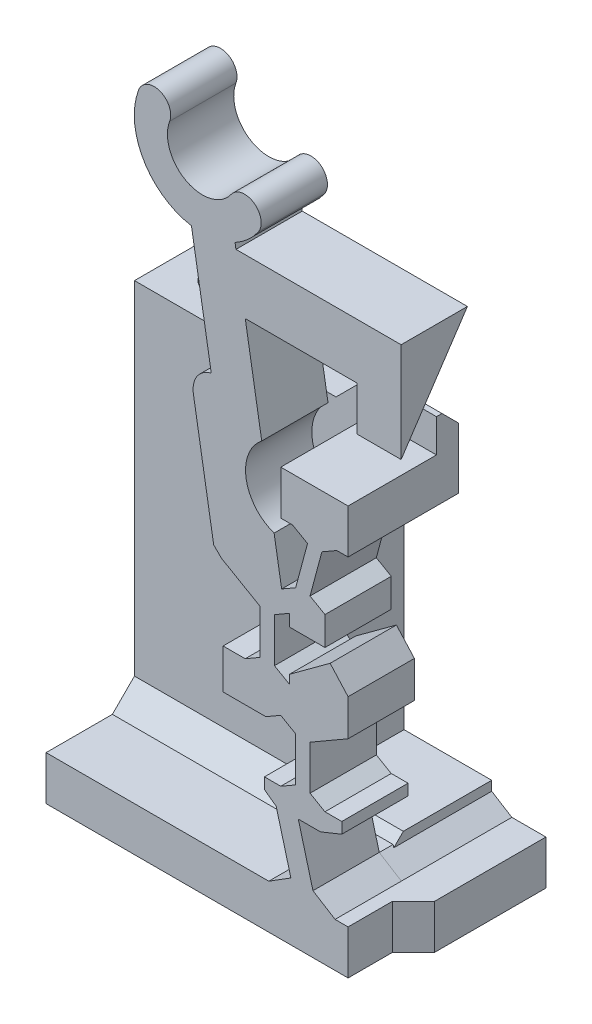
SolidWorks part; units mm, degrees
material "Nylon 6/12"
ref_plane "Front Plane" through (0, 0, 0) normal (0, 0, 1) x (1, 0, 0)
ref_plane "Top Plane" through (0, 0, 0) normal (0, 1, 0) x (1, 0, 0)
ref_plane "Right Plane" through (0, 0, 0) normal (1, 0, 0) x (0, 0, -1)
sketch "Sketch-SkeletonConfigUp" plane through (0, 0, 0) normal (0, 0, 1) x (1, 0, 0)
  line L0 (0, 0) -> (0, -50000) construction
  line L1 (0, 0) -> (4.5811, 6.2164) construction
  line L2 (9.8143, 13.3177) -> (4.5811, 13.945) construction
  line L3 (4.5811, 13.945) -> (2.9713, 10.4094) construction
  line L4 (2.9713, 10.4094) -> (4.5811, 6.2164) construction
  line L5 (4.5811, 13.945) -> (6.2429, 19.1409) construction
  line L6 (2.9713, 10.4094) -> (0.0405, 27.8193) construction
  line L7 (4.5811, 6.2164) -> (9.8143, 13.3177) construction
  line L8 (-587.3593, -797.0242) -> (9.8143, 13.3177) construction
  dimension "D2" = 7.7221
  dimension "D3" = 8.8212
  dimension "D4" = 5.2707
  dimension "D5" = 119.553
  dimension "D6" = 3.8848
  dimension "D7" = 5.4552
  dimension "D8" = 17.6549
  dimension "D9" = 4.4914
  dimension "D10" = 6.745
  dimension "D11" = 145.964
  dimension "D12" = 143.612
sketch "Sketch-SkeletonConfigDown" plane through (0, 0, 0) normal (0, 0, 1) x (1, 0, 0)
  line L0 (0, 0) -> (0, -50000) construction
  line L1 (0, 0) -> (4.5811, 6.2164) construction
  line L2 (9.8143, 13.3177) -> (4.5811, 13.945) construction
  line L3 (4.5811, 13.945) -> (6.1909, 10.4094) construction
  line L4 (6.1909, 10.4094) -> (4.5811, 6.2164) construction
  line L5 (4.5811, 13.945) -> (1.753, 18.6098) construction
  line L6 (6.1909, 10.4094) -> (-8.8652, 19.6294) construction
  line L7 (4.5811, 6.2164) -> (9.8143, 13.3177) construction
  line L8 (-589.9357, -800.5203) -> (9.8143, 13.3177) construction
  dimension "D2" = 7.7221
  dimension "D3" = 8.8212
  dimension "D4" = 5.2707
  dimension "D5" = 119.553
  dimension "D6" = 3.8848
  dimension "D7" = 5.4552
  dimension "D8" = 17.6549
  dimension "D9" = 4.4914
  dimension "D10" = 6.745
  dimension "D11" = 145.964
  dimension "D1" = 143.612
ref_plane "Plane-Cam Base" through (9.128, 0, 0) normal (1, 0, 0) x (0, 0, -1)
ref_plane "Plane-Down-to-Up Derailleur Clearance" through (6.628, 0, 0) normal (1, 0, 0) x (0, 0, -1)
ref_plane "Plane-Cam Cavity Roof" through (5.128, 0, 0) normal (1, 0, 0) x (0, 0, -1)
sketch "Sketch-SwitchBossUp" plane through (0, 0, 0) normal (0, 0, 1) x (1, 0, 0)
  line L0 (3.5811, 11.4759) -> (3.5811, 12.945) construction
  line L5 (5.5811, 12.5552) -> (5.5811, 11.263)
  line L7 (1.5115, 25.1048) -> (1.5536, 24.8548)
  line L8 (-0.4607, 24.7728) -> (0.4359, 19.4465)
  line L9 (2.9713, 10.4094) -> (0.0405, 27.8193) construction
  line L11 (0.1364, 21.2256) -> (2.1086, 21.5576) construction
  line L15 (6.628, -23.7286) -> (6.628, 23.7286) construction
  line L16 (2.9713, 10.4094) -> (4.5811, 6.2164) construction
  line L17 (3.5811, 12.945) -> (3.5811, 14.945) construction
  line L18 (5.5811, 12.945) -> (5.5811, 14.945) construction
  line L19 (4.2561, 13.945) -> (4.9061, 13.945) construction
  line L20 (3.5811, 14.945) -> (5.5811, 14.945) construction
  line L21 (3.5811, 12.945) -> (5.5811, 12.945) construction
  line L22 (4.5811, 12.945) -> (4.5811, 14.945) construction
  line L23 (4.5811, 6.2164) -> (8.5405, 7.1023) construction
  line L24 (1.9713, 9.4094) -> (1.9713, 11.4094) construction
  line L25 (3.9713, 9.4094) -> (3.9713, 11.4094) construction
  line L26 (3.9713, 9.4094) -> (1.9713, 9.4094) construction
  line L27 (1.9713, 11.4094) -> (3.9713, 11.4094) construction
  line L28 (3.5811, 7.2164) -> (5.5811, 7.2164) construction
  line L29 (3.5811, 7.2164) -> (3.5811, 5.2164) construction
  line L30 (5.5811, 7.2164) -> (5.5811, 5.2164) construction
  line L31 (3.5811, 5.2164) -> (5.5811, 5.2164) construction
  line L32 (4.9061, 6.2164) -> (4.2561, 6.2164) construction
  line L40 (3.2963, 10.4094) -> (2.6463, 10.4094) construction
  line L66 (0.0405, 27.8193) -> (0.0405, 50027.8193) construction
  line L74 (0.5455, 12.7717) -> (-0.3728, 18.2264)
  line L75 (0.3841, 13.7302) -> (2.3564, 14.0622) construction
  line L76 (5.5811, 11.263) -> (5.5811, 12.5552) construction
  line L77 (5.5811, 7.6061) -> (6.628, 8.2105)
  line L80 (5.8152, 10.763) -> (6.628, 9.8603)
  line L81 (9.128, 1033.2419) -> (9.128, 20.0586) construction
  line L85 (6.9307, 9.5241) -> (8.5405, 7.7363) construction
  line L88 (5.7256, 17.3347) -> (6.628, 17.3347)
  line L92 (3.7762, 8.3129) -> (6.9307, 9.5241) construction
  line L98 (1.9713, 9.0197) -> (0.9713, 9.0197)
  line L99 (0.9713, 9.0197) -> (0.9713, 7.2164)
  line L100 (0.9713, 7.2164) -> (2.9061, 7.2164)
  line L101 (4.5811, 6.2164) -> (6.9307, 9.5241) construction
  line L103 (0.0405, 27.8193) -> (1.9448, 26.4638) construction
  line L104 (6.9307, 9.5241) -> (8.5405, 7.7363) construction
  line L107 (1.9713, 9.4094) -> (1.9713, 9.0197) construction
  line L109 (0.0405, 27.8193) -> (-2.1498, 28.6358) construction
  line L111 (6.628, 9.8603) -> (6.628, 8.2105)
  line L112 (6.628, 9.8603) -> (6.9307, 9.5241) construction
  line L113 (2.8424, 4.8267) -> (2.8424, 4.3267)
  line L114 (7.3693, 7.7363) -> (7.3563, 7.7363) construction
  line L121 (5.0383, -1.1653) -> (5.0383, 1.4614) construction
  line L122 (9.028, 22.3548) -> (9.028, 20.3548)
  line L127 (5.5811, 15.3347) -> (5.5811, 14.945) construction
  line L130 (6.0388, 0.837) -> (6.628, 0.837)
  line L132 (2.8424, 4.3267) -> (3.3749, 3.937)
  line L133 (2.9713, 10.4094) -> (6.1909, 10.4094) construction
  line L134 (4.5811, 10.4094) -> (4.5811, 13.945) construction
  line L135 (4.5811, 10.4094) -> (4.5811, 6.2164) construction
  line L136 (0.8973, 12.4192) -> (0.5455, 12.7717)
  line L137 (3.9713, 9.4094) -> (5.5811, 7.2164) construction
  line L139 (5.8152, 10.763) -> (3.9713, 9.4094)
  line L141 (4.0386, 1.4604) -> (3.0388, 0.8347)
  line L142 (3.0388, 0.8347) -> (3.0388, -1.1653)
  line L143 (9.128, 20.0586) -> (9.128, 18.3333) construction
  line L145 (9.128, 16.6071) -> (9.128, -49992.4167) construction
  line L147 (5.5811, 11.263) -> (5.5811, 12.5552) construction
  line L150 (3.0388, -1.1653) -> (5.0383, -1.1653)
  line L151 (3.3749, 3.937) -> (4.3749, 3.937) construction
  line L152 (4.792, 14.945) -> (4.2561, 12.945)
  line L153 (5.442, 14.945) -> (4.9061, 12.945)
  line L157 (3.5811, 17.3347) -> (3.5811, 15.3347)
  line L158 (6.117, 15.3347) -> (6.628, 15.3347)
  line L162 (3.2963, 11.4094) -> (3.2963, 9.4094)
  line L164 (2.6463, 11.4094) -> (2.6463, 9.4094)
  line L169 (4.2561, 7.2164) -> (4.2561, 5.2164)
  line L170 (4.9061, 5.2164) -> (4.9061, 7.2164)
  line L175 (4.2561, 7.2164) -> (3.5811, 7.6061)
  line L176 (4.9061, 7.2164) -> (5.5811, 7.6061)
  line L177 (5.5811, 7.2164) -> (5.5811, 7.6061) construction
  line L179 (4.2561, 5.2164) -> (3.5811, 4.8267)
  line L180 (3.5811, 5.2164) -> (3.5811, 4.8267) construction
  line L181 (3.5811, 4.8267) -> (2.8424, 4.8267)
  line L183 (4.9061, 5.2164) -> (5.5811, 4.8267)
  line L184 (5.5811, 5.2164) -> (5.5811, 4.8267) construction
  line L186 (9.128, -23.7286) -> (9.128, 23.7286) construction
  line L187 (2.6463, 9.4094) -> (1.9713, 9.0197)
  line L188 (3.2963, 9.4094) -> (3.9713, 9.0197)
  line L189 (3.2963, 11.4094) -> (3.9713, 11.7991)
  line L190 (2.6463, 11.4094) -> (0.8973, 12.4192)
  line L191 (3.9713, 11.4094) -> (3.9713, 11.7991) construction
  line L192 (3.9713, 11.7991) -> (3.9713, 11.263)
  line L193 (4.9061, 12.945) -> (5.5811, 12.5552)
  line L194 (4.2561, 12.945) -> (3.6203, 12.5779)
  line L195 (3.9713, 11.263) -> (5.5811, 11.263)
  line L196 (3.9713, 9.4094) -> (3.9713, 9.0197)
  line L197 (3.5811, 7.2164) -> (3.5811, 7.6061) construction
  line L199 (3.5811, 7.6061) -> (2.9061, 7.2164)
  line L201 (2.8424, 4.3267) -> (2.8424, 3.937) construction
  line L202 (2.8424, 3.937) -> (3.3749, 3.937) construction
  line L204 (5.0383, 1.437) -> (3.0388, 1.437) construction
  line L205 (3.0388, 1.437) -> (3.0388, 0.8347) construction
  line L206 (5.0383, 1.4614) -> (6.0388, 0.837)
  line L207 (9.128, 18.3333) -> (9.128, 16.6071) construction
  line L208 (6.628, -1.1653) -> (6.628, 0.837)
  line L209 (9.128, 20.0586) -> (9.128, 16.6071) construction
  line L211 (5.0383, 1.4614) -> (4.3749, 3.937)
  line L212 (4.0386, 1.4604) -> (3.3749, 3.937)
  line L214 (4.792, 14.945) -> (4.1169, 15.3347)
  line L215 (4.1169, 15.3347) -> (3.5811, 15.3347)
  line L216 (5.442, 14.945) -> (6.117, 15.3347)
  line L217 (5.5811, 12.945) -> (5.5811, 12.5552) construction
  line L218 (5.442, 14.945) -> (5.442, 15.3347) construction
  line L219 (6.117, 15.3347) -> (4.1169, 15.3347) construction
  line L221 (9.028, 22.3548) -> (9.028, 24.8548)
  line L224 (3.5811, 17.3347) -> (5.7256, 17.3347)
  line L232 (6.628, 15.3347) -> (6.628, 17.3347)
  line L233 (6.628, -1.1653) -> (5.0383, -1.1653)
  line L236 (1.5536, 24.8548) -> (9.028, 24.8548)
  line L240 (4.3749, 3.937) -> (5.3749, 3.937)
  line L241 (5.3749, 3.937) -> (6.3424, 4.3267)
  line L248 (7.028, 22.3548) -> (1.9744, 22.3548)
  line L249 (1.9744, 22.3548) -> (2.7198, 17.9273)
  line L250 (9.028, 20.3548) -> (7.028, 20.3548)
  line L251 (7.028, 20.3548) -> (7.028, 22.3548)
  line L252 (3.2801, 14.5986) -> (3.6203, 12.5779)
  line L367 (5.5811, 4.8267) -> (6.3424, 4.8267)
  line L368 (6.3424, 4.8267) -> (6.3424, 4.3267)
  arc A0 (1.5115, 25.1048) -> (2.5558, 26.0289) centre (0.0405, 27.8193) ccw
  arc A1 (-0.4607, 24.7728) -> (-2.8525, 28.8978) centre (0.0405, 27.8193) cw
  arc A2 (-2.8525, 28.8978) -> (-1.447, 28.3738) centre (-2.1498, 28.6358) cw
  arc A3 (2.5558, 26.0289) -> (1.3338, 26.8987) centre (1.9448, 26.4638) ccw
  arc A4 (-1.447, 28.3738) -> (1.3338, 26.8987) centre (0.0405, 27.8193) ccw
  arc A5 (3.5811, 12.945) -> (3.5811, 14.945) centre (3.1778, 13.945) ccw construction
  arc A6 (5.5811, 12.945) -> (5.5811, 14.945) centre (5.9843, 13.945) cw construction
  arc A7 (2.5293, 9.921) -> (1.9713, 11.4094) centre (1.568, 10.4094) ccw construction
  arc A8 (3.9713, 11.4094) -> (3.9713, 9.4094) centre (4.3745, 10.4094) ccw construction
  arc A9 (3.5811, 7.2164) -> (3.5811, 5.2164) centre (3.1779, 6.2164) cw construction
  arc A10 (5.5811, 7.2164) -> (5.5811, 5.2164) centre (5.9844, 6.2164) ccw construction
  arc A19 (-0.3728, 18.2264) -> (0.4359, 19.4465) centre (0.6836, 18.4042) cw
  circle A28 centre (0.0405, 27.8193) radius 2.3375 construction
  arc A29 (1.9713, 9.4094) -> (2.5293, 9.921) centre (1.568, 10.4094) ccw construction
  arc A30 (3.2801, 14.5986) -> (2.7198, 17.9273) centre (3.9114, 16.4164) cw
  point P53 (4.5811, 13.945)
  point P63 (2.9713, 10.4094)
  point P93 (1.1225, 21.3916)
  dimension "D23" = 1.5875
  dimension "D24" = 0.75
  dimension "D2" = 2
  dimension "D5" = 2
  dimension "D6" = 0.65
  dimension "D8" = 42
  dimension "D16" = 42
  dimension "D27" = 120
  dimension "D28" = 120
  dimension "D29" = 120
  dimension "D30" = 120
  dimension "D31" = 120
  dimension "D32" = 120
  dimension "D33" = 120
  dimension "D34" = 120
  dimension "D17" = 0.5
  dimension "D21" = 2
  dimension "D22" = 1
  dimension "D38" = 2
  dimension "D39" = 0.5
  dimension "D40" = 60
  dimension "D41" = 1
  dimension "D42" = 45
  dimension "D43" = 120
  dimension "D10" = 15
  dimension "D12" = 2.5
  dimension "D13" = 1
  dimension "D19" = 1
  dimension "D25" = 15
  dimension "D26" = 120
  dimension "D35" = 120
  dimension "D20" = 3
  dimension "D48" = 2
  dimension "D49" = 0.6
  dimension "D82" = 1
  dimension "D83" = 3.5
  dimension "D14" = 2.5
  dimension "D15" = 0.25
  dimension "D7" = 2
  dimension "D9" = 2
extrude "Boss-Switch Body" add sketch "Sketch-SwitchBossUp" along normal blind 3
sketch "Sketch1" plane through (0, 0, 0) normal (0, 0, -1) x (-1, 0, 0)
  line L1 (-7.5811, -1.1653) -> (0.4122, -1.1653)
  line L2 (-7.5811, -1.1653) -> (-7.5811, 0.837)
  line L4 (0.4122, -1.1653) -> (0.4122, 0.8347)
  line L5 (-3.5811, 18.8347) -> (-7.5811, 18.8347)
  line L10 (-7.5811, 18.8347) -> (-7.5811, 15.3347)
  line L11 (-4.0386, 1.4604) -> (-5.0386, 1.4604)
  line L12 (-7.5811, 15.3347) -> (-3.5811, 15.3347)
  line L13 (-4.0386, 1.4604) -> (-3.0388, 0.8347)
  line L14 (-3.5811, 15.3347) -> (-3.5811, 18.8347)
  line L20 (-4.3749, 3.937) -> (-5.0383, 1.4614) construction
  line L22 (-3.0388, -1.1653) -> (-6.628, -1.1653) construction
  line L23 (-3.0388, 0.8347) -> (0.4122, 0.8347)
  line L24 (-5.0386, 1.4604) -> (-6.0388, 0.837)
  line L25 (-6.0388, 0.837) -> (-7.5811, 0.837)
  dimension "D1" = 3.5
extrude "Boss-Flange Width" add sketch "Sketch1" along normal blind 5
ref_plane "Plane-Sta2Sit Groove" through (0.0405, 0, 0) normal (1, 0, 0) x (0, 0, -1)
ref_plane "Plane-Cam Outer Surface" through (-12.0395, 0, 0) normal (1, 0, 0) x (0, 0, -1)
ref_plane "Plane-FlangeTop" through (-7.0395, 0, 0) normal (1, 0, 0) x (0, 0, -1)
sketch "Sketch2" plane through (-7.0395, 0, 0) normal (1, 0, 0) x (0, 0, -1)
  line L0 (5, 15.3347) -> (-3, 15.3347) construction
  line L1 (5, 17.3347) -> (1, 17.3347)
  line L2 (5, 17.3347) -> (5, 15.3347)
  line L3 (5, 15.3347) -> (1, 15.3347)
  line L4 (1, 17.3347) -> (1, 15.3347)
  line L5 (-3, -1.1653) -> (-3, 0.837) construction
  line L11 (5, 0.8347) -> (-3, 0.8347)
  line L12 (5, 0.8347) -> (5, -1.1653)
  line L13 (5, -1.1653) -> (-3, -1.1653)
  line L14 (-3, 0.8347) -> (-3, -1.1653)
  line L15 (0, 10.4094) -> (0, 27.8193) construction
  line L17 (5, 0.837) -> (5, -1.1653) construction
  line L18 (-3, 0.8347) -> (0, 0.8347) construction
  dimension "D1" = 1
  dimension "D2" = 2
extrude "Boss-Flange Height" add sketch "Sketch2" along normal up to surface (11.6675 mm away)
sketch "Sketch10" plane through (0, 15.3347, 0) normal (0, 1, 0) x (1, 0, 0)
  line L0 (9.128, -23.7286) -> (9.128, 23.7286) construction
  line L1 (7.5811, 5) -> (5.128, 5)
  line L2 (7.5811, 5) -> (7.5811, 2)
  line L3 (7.5811, 2) -> (5.128, 2)
  line L5 (4.628, 7) -> (4.628, 1) construction
  line L6 (3.5811, 1) -> (-7.0395, 1) construction
  line L8 (5.128, 5) -> (5.128, 2)
  dimension "D1" = 1
  dimension "D2" = 0.5
  dimension "D3" = 4.5
extrude "Cut-Up-To-Down Derailleur Clearance" cut sketch "Sketch10" along normal up to next
sketch "Sketch17" plane through (0, 15.3347, 0) normal (0, -1, 0) x (1, 0, 0)
  line L0 (5.128, -5) -> (-7.0395, -5)
  line L1 (5.128, -5) -> (-7.0395, -5) construction
  line L2 (-7.0395, -5) -> (-7.0395, -1)
  line L3 (-7.0395, -1) -> (5.128, -1)
  line L4 (5.128, -1) -> (5.128, -5)
  line L5 (-7.0395, -1) -> (-7.0395, -5) construction
extrude "Boss-Flange Support" add sketch "Sketch17" along normal up to surface (14.5 mm away) up to face at (-2.0003, 0.8347, -1)
sketch "Sketch-HolePositions" plane through (0, -1.1653, 0) normal (0, -1, 0) x (1, 0, 0)
  line L0 (-7.0395, -3) -> (7.5811, -3) construction
  line L1 (7.5811, -5) -> (-7.0395, -5) construction
  line L2 (7.5811, -5) -> (7.5811, 0) construction
  line L4 (-7.0395, -22.2167) -> (-7.0395, 22.2167) construction
  point P6 (-5.0395, -3)
  point P7 (-0.5395, -3)
  dimension "D1" = 2
  dimension "D2" = 4.5
  dimension "D3" = 2
sketch "Sketch6" plane through (0, -1.1653, 0) normal (0, -1, 0) x (-1, 0, 0)
  point P0 (5.0395, 3)
  point P3 (0.5395, 3)
hole_wizard "Tap Drill for M2x0.4 Tap1" positions "Sketch6" profile "Sketch5" hole size "M2x0.4" standard "ANSI Metric" end condition through all
sketch "Sketch5" plane through (-5.0395, -1.1653, -3) normal (1, 0, 0) x (0, 0, -1)
  line L0 (0, 0) -> (0, 30.5511)
  line L1 (0, 30.5511) -> (0.8, 30.5511)
  line L2 (0.8, 30.5511) -> (0.8, 0)
  line L5 (0.8, 0) -> (0, 0)
  line L11 (0, -6.35) -> (0, 107.95) construction
  dimension "Thru Hole Dia." = 1.6
  dimension "Thru Hole Depth" = 30.5511
sketch "Sketch9" plane through (0, -1.1653, 0) normal (0, -1, 0) x (1, 0, 0)
  point P0 (-5.0395, -3)
  point P3 (-0.5395, -3)
hole_wizard "M2 Clearance Hole2" positions "Sketch9" profile "Sketch8" hole size "M2" standard "ANSI Metric"
sketch "Sketch8" plane through (-5.0395, -1.1653, -3) normal (1, 0, 0) x (0, 0, -1)
  line L0 (0, 0) -> (0, 15.721)
  line L1 (0, 15.721) -> (1.2, 15)
  line L2 (1.2, 15) -> (1.2, 0)
  line L5 (1.2, 0) -> (0, 0)
  line L10 (0, 15.721) -> (-1.2, 15) construction
  line L11 (0, -6.35) -> (0, 107.95) construction
  dimension "Hole Dia." = 2.4
  dimension "Hole Depth" = 15
  dimension "Drill Angle" = 118
sketch "Sketch-Measurements for Derailleur Ramps" [suppressed] plane through (0, 0, 0) normal (0, 0, 1) x (1, 0, 0)
  line L0 (3.184, 15.1695) -> (2.4687, 19.4188)
  line L1 (2.8264, 17.2941) -> (1.8402, 17.1281)
  line L2 (2.9713, 10.4094) -> (0.0405, 27.8193) construction
  line L3 (1.8402, 17.1281) -> (-1.3081, 15.0016)
  line L4 (6.1909, 10.4094) -> (-8.8652, 19.6294) construction
  line L5 (1.8402, 17.1281) -> (2.6012, 12.6077)
  line L6 (2.6012, 12.6077) -> (-1.3081, 15.0016)
  line L7 (0.2661, 16.0649) -> (0.2661, 17.1281)
  line L8 (0.2661, 17.1281) -> (1.8402, 17.1281)
  line L9 (6.1909, 10.4094) -> (2.9713, 10.4094)
  line L10 (5.386, 8.3129) -> (3.7762, 8.3129)
  line L11 (2.6116, 18.5698) -> (1.5115, 25.1048) construction
  line L12 (6.1909, 10.4094) -> (4.5811, 6.2164) construction
  line L13 (4.5811, 8.3129) -> (4.5811, 8.7912)
  line L14 (4.5811, 6.2164) -> (5.386, 8.3129)
  line L15 (2.9713, 10.4094) -> (4.5811, 6.2164) construction
  line L16 (3.7762, 8.3129) -> (4.5811, 6.2164)
  line L17 (5.386, 8.3129) -> (5.386, 8.7912)
  dimension "D1" = 1.5742
  dimension "D2" = 0.8049
ref_plane "Plane1" through (0, 7.1023, 0) normal (0, 1, 0) x (1, 0, 0)
ref_plane "Plane-Cantilever Cut" [suppressed] through (7.0848, 8.5204, -1.9058) normal (-0.6301, -0.7578, 0.1695) x (-0.7765, 0.6151, -0.1368)
sketch "Sketch14" [suppressed] plane through (7.0848, 8.5204, -1.9058) normal (-0.6301, -0.7578, 0.1695) x (-0.7765, 0.6151, -0.1368)
  line L0 (2.3023, -1.6911) -> (-0.3551, -1.6911)
  line L2 (2.3023, -4.3362) -> (2.3023, -1.6911)
  line L3 (-0.3551, -1.6911) -> (-0.3551, -4.4608)
  line L5 (-0.3551, -4.4608) -> (1.0087, -5.0843)
  line L6 (1.0087, -5.0843) -> (2.3023, -4.3362)
extrude "Cut-Down-to-Up Cantilever Slope" [suppressed] cut sketch "Sketch14" against normal up to next
ref_plane "Plane-Symmetry Plane" through (0, 0, 1.5) normal (0, 0, 1) x (1, 0, 0)
sketch "Sketch-Cable Center Point" plane through (0, 0, 1.5) normal (0, 0, 1) x (1, 0, 0)
  line L0 (0.0405, 27.8193) -> (0.1722, 27.0366)
  line L1 (2.9713, 10.4094) -> (0.0405, 27.8193) construction
  point P0 (0.0405, 27.8193)
  dimension "D1" = 0.7937
chamfer "Chamfer-Flange Support" distance 1.5 angle 45 1 edges at (3.5811, 17.3347, -3)
chamfer "Chamfer-Flange Support 2" distance 1.5 angle 45 2 edges at (5.128, 17.0847, -2) (5.128, 15.3347, -1.5)
chamfer "Chamfer-Flange Support 3" distance 1 angle 45 1 edges at (-2.0003, 0.8347, -1)
chamfer "Chamfer7" [suppressed] distance 1 angle 45
sketch "Sketch23" plane through (0, 0, -1) normal (0, 0, 1) x (1, 0, 0)
  line L0 (5.128, 1.8347) -> (1.1605, 1.8347)
  line L1 (-7.0395, 1.8347) -> (5.128, 1.8347) construction
  line L2 (1.1605, 1.8347) -> (1.1605, 13.8347)
  line L3 (1.1605, 13.8347) -> (5.128, 13.8347)
  line L4 (5.128, 13.8347) -> (5.128, 1.8347)
  line L5 (0.6605, -1.1653) -> (0.6605, 13.8347) construction
  dimension "D1" = 0.5
extrude "Cut-Gap for Printing" cut sketch "Sketch23" against normal through all
sketch "Sketch25" plane through (0, 0, 0) normal (0, 0, 1) x (1, 0, 0)
  line L0 (6.628, 15.3347) -> (7.5811, 15.3347)
  line L1 (7.5811, 15.3347) -> (7.5811, 18.8347)
  line L2 (7.5811, 18.8347) -> (6.628, 18.8347)
  line L3 (6.628, -23.7286) -> (6.628, 23.7286) construction
  line L4 (7.5811, 18.8347) -> (3.5811, 18.8347) construction
  line L5 (6.628, 18.8347) -> (6.628, 15.3347)
  line L6 (7.5811, 18.8347) -> (7.5811, 15.3347) construction
extrude "Cut-Derailleur Clearance" cut sketch "Sketch25" against normal through all
chamfer "Chamfer8" distance 1 angle 45 1 edges at (6.628, -0.1641, 0)
ref_plane "Plane2" through (-3.0866, 5.589, 8.3835) normal (0.2929, -0.5304, -0.7956) x (-0.9561, -0.1625, -0.2437)
sketch "Sketch26" plane through (-3.0866, 5.589, 8.3835) normal (0.2929, -0.5304, -0.7956) x (-0.9561, -0.1625, -0.2437)
  line L0 (-7.553, 20.6804) -> (-7.553, 14.9094)
  line L1 (-12.6703, 20.6804) -> (-5.5238, 20.6804) construction
  line L3 (-7.553, 14.9094) -> (-20.0302, 14.9094)
  line L4 (-20.0302, 14.9094) -> (-20.0302, 20.6804)
  line L5 (-20.0302, 20.6804) -> (-7.553, 20.6804)
  point P8 (-7.553, 16.9362)
extrude "Cut-Up-to-Down Cantilever Slope" cut sketch "Sketch26" along normal up to next
sketch "Sketch27" plane through (5.128, 0, 0) normal (1, 0, 0) x (0, 0, -1)
  line L0 (3.5, 18.8347) -> (3.5, 13.8347) construction
  line L1 (2.5, 18.8347) -> (5, 18.8347)
  line L2 (2.5, 18.8347) -> (2.5, 13.8347)
  line L3 (2.5, 13.8347) -> (5, 13.8347)
  line L4 (5, 18.8347) -> (5, 13.8347)
  dimension "D1" = 1
extrude "Cut-Wide Derailleur Clearance" cut sketch "Sketch27" against normal blind 4 and the other way through all
chamfer "Chamfer9" distance 1.25 angle 45 1 edges at (4.8545, 18.8347, -2.5)
sketch "Sketch28" plane through (0, 0, -1) normal (0, 0, 1) x (1, 0, 0)
  line L0 (3.5811, 18.8347) -> (6.628, 18.8347)
  line L1 (6.628, 18.8347) -> (6.628, 17.3347)
  line L2 (6.628, 17.3347) -> (3.5811, 17.3347)
  line L3 (3.5811, 17.3347) -> (3.5811, 18.8347)
extrude "Cut-Extrude1" cut sketch "Sketch28" along normal up to surface (1 mm away) up to face at (5.1045, 18.0847, 0)
equation "\"axle-diameter\"=2"
equation "\"switch-thickness\"=12"
equation "\"base-width\"=4.0"
equation "\"axle-bushing-radius\"=3"
equation "\"clearance\"= 0.25"
equation "\"arm-width\"=1.5"
equation "\"min-diameter\"=70"
equation "\"alpha\"=143.6120"
equation "\"gamma\"=119.5526"
equation "\"delta\"=145.9637"
equation "\"epsilon\"=6.7452"
equation "\"l_AB\"=8.8212"
equation "\"l_AC\"=4.4914"
equation "\"l_BD\"=5.2707"
equation "\"l_CD\"=3.8848"
equation "\"l_CE\"=17.6549"
equation "\"l_DF\"=5.4552"
equation "\"l_OA\"=7.7221"
equation "\"D2@Sketch-SkeletonConfigUp\" = \"l_OA\""
equation "\"D3@Sketch-SkeletonConfigUp\" = \"l_AB\""
equation "\"D4@Sketch-SkeletonConfigUp\" = \"l_BD\""
equation "\"D5@Sketch-SkeletonConfigUp\" = \"gamma\""
equation "\"D6@Sketch-SkeletonConfigUp\" = \"l_CD\""
equation "\"D7@Sketch-SkeletonConfigUp\" = \"l_DF\""
equation "\"D8@Sketch-SkeletonConfigUp\" = \"l_CE\""
equation "\"D9@Sketch-SkeletonConfigUp\" = \"l_AC\""
equation "\"D_groove\"=3.175"
equation "\"D7@Sketch-SkeletonConfigDown\" = \"l_DF\""
equation "\"D6@Sketch-SkeletonConfigDown\" = \"l_CD\""
equation "\"D2@Sketch-SkeletonConfigDown\" = \"l_OA\""
equation "\"D3@Sketch-SkeletonConfigDown\" = \"l_AB\""
equation "\"D9@Sketch-SkeletonConfigDown\" = \"l_AC\""
equation "\"D8@Sketch-SkeletonConfigDown\" = \"l_CE\""
equation "\"D5@Sketch-SkeletonConfigDown\" = \"gamma\""
equation "\"D4@Sketch-SkeletonConfigDown\" = \"l_BD\""
equation "\"D1@Sketch-SkeletonConfigDown\" = \"alpha\""
equation "\"hinge_length\"=1.5"
equation "\"hinge_depth\"=0.25"
equation "\"D10@Sketch-SkeletonConfigUp\"=\"epsilon\""
equation "\"D11@Sketch-SkeletonConfigUp\"=\"delta\""
equation "\"D12@Sketch-SkeletonConfigUp\"=\"alpha\""
equation "\"D11@Sketch-SkeletonConfigDown\"=\"delta\""
equation "\"D10@Sketch-SkeletonConfigDown\"=\"epsilon\""
equation "\"EE_dx\"=8.9056"
equation "\"EE_dy\"=8.1898"
equation "\"r_groove\"=\"D_groove\"/2"
equation "\"t_wall\"=25.4/16"
equation "\"width_lower\"=\"D_groove\"+\"t_wall\""
equation "\"cable_to_bottom\"=30.6257"
equation "\"switch_EE-up_base_dy\"=24"
equation "\"switch_EE-down_base_dy\"=16"
equation "\"D_axle\"=25.4/8"
equation "\"D_up_to_down\"=16"
equation "\"D_down_to_up\"=25"
equation "\"t_cam_base\"=7.5"
equation "\"D23@Sketch-SwitchBossUp\"=\"D_groove\"/2"
equation "\"D1@Sketch-Cable Center Point\"=\"D_groove\"/4"
